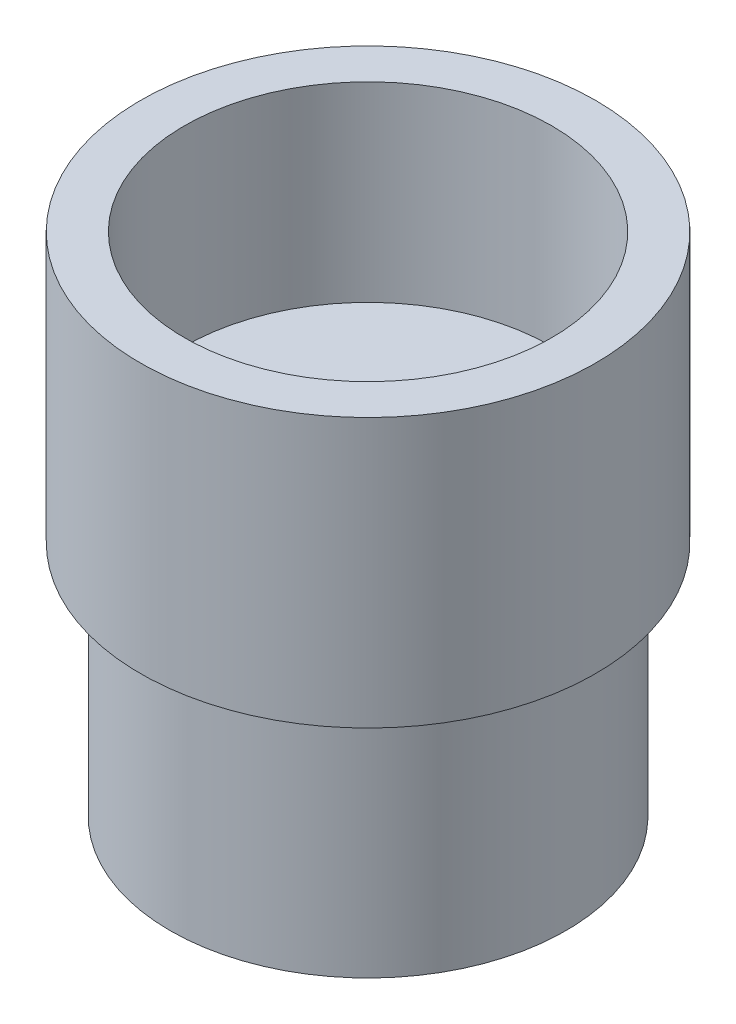
SolidWorks part; units mm, degrees
ref_plane "Front Plane" through (0, 0, 0) normal (0, 0, 1) x (1, 0, 0)
ref_plane "Top Plane" through (0, 0, 0) normal (0, 1, 0) x (1, 0, 0)
ref_plane "Right Plane" through (0, 0, 0) normal (1, 0, 0) x (0, 0, -1)
sketch "Sketch1" plane through (0, 0, 0) normal (0, 0, 1) x (1, 0, 0)
  line L0 (0, 0) -> (0, 65) construction
  line L2 (23.5712, 0) -> (25.4, 0)
  line L3 (23.5712, 0) -> (23.5712, 30.48)
  line L4 (23.5712, 30.48) -> (25.4, 30.48)
  line L5 (25.4, 0) -> (25.4, 30.48)
  line L6 (23.5712, 30.48) -> (29.21, 30.48)
  line L7 (23.5712, 30.48) -> (23.5712, 65)
  line L8 (23.5712, 65) -> (29.21, 65)
  line L9 (29.21, 30.48) -> (29.21, 65)
  line L10 (23.5712, 40.48) -> (0, 40.48)
  line L11 (23.5712, 40.48) -> (23.5712, 30.48)
  line L12 (23.5712, 30.48) -> (0, 30.48)
  line L13 (0, 40.48) -> (0, 30.48)
  dimension "D1" = 65
  dimension "D2" = 50.8
  dimension "D3" = 1.8288
  dimension "D4" = 30.48
  dimension "D5" = 3.81
  dimension "D6" = 10
revolve "Revolve1" add sketch "Sketch1" angle 360 about L0 region at (24.4856, 15.24, 0) region at (26.3906, 47.74, 0) region at (11.7856, 35.48, 0)
